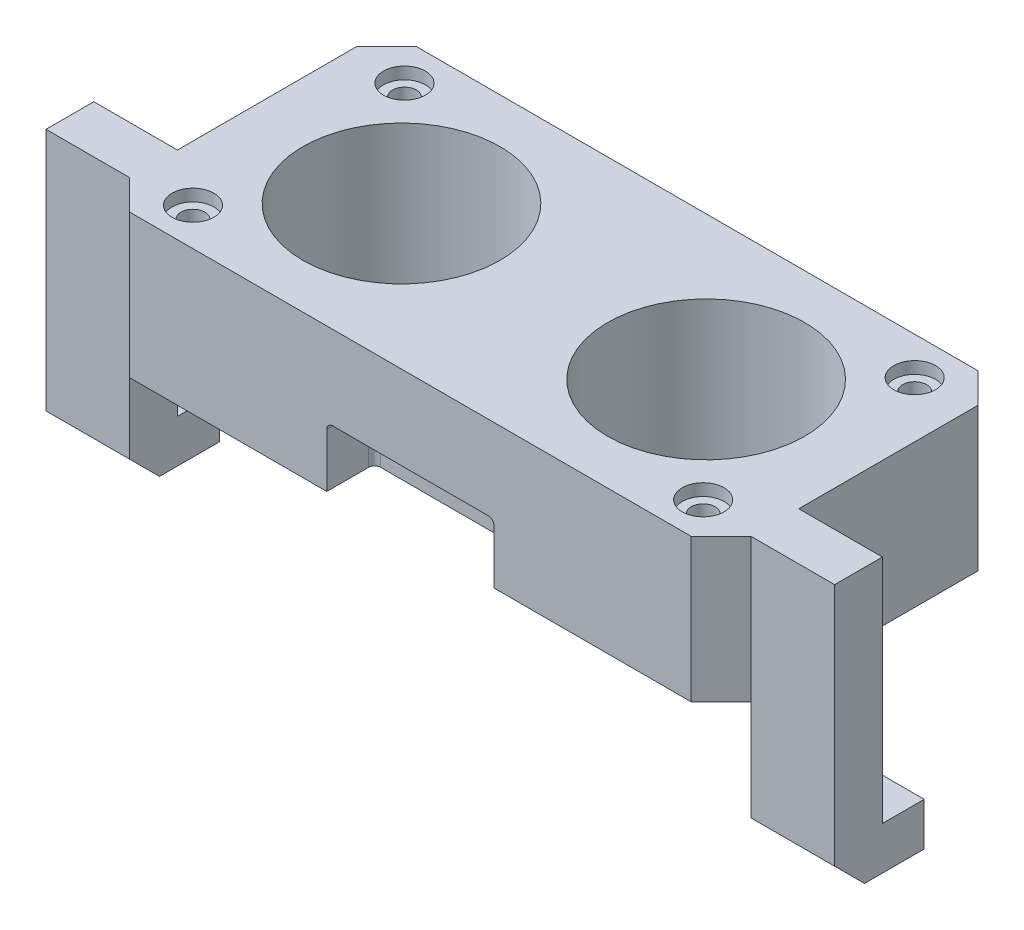
SolidWorks part; units mm, degrees
ref_plane "Front Plane" through (0, 0, 0) normal (0, 0, 1) x (1, 0, 0)
ref_plane "Top Plane" through (0, 0, 0) normal (0, 1, 0) x (1, 0, 0)
ref_plane "Right Plane" through (0, 0, 0) normal (1, 0, 0) x (0, 0, -1)
sketch "Sketch1" plane through (0, 0, 0) normal (0, 1, 0) x (1, 0, 0)
  line L0 (-12.75, 0) -> (12.75, 0) construction
  line L1 (-26, 12) -> (26, 12)
  line L2 (-26, 12) -> (-26, -12)
  line L3 (-26, -12) -> (26, -12)
  line L4 (26, 12) -> (26, -12)
  line L5 (-26, 12) -> (26, -12) construction
  line L6 (-26, -12) -> (26, 12) construction
  circle A0 centre (12.75, 0) radius 8.25
  circle A1 centre (-12.75, 0) radius 8.25
  point P0 (0, 0)
  point P9 (0, 0)
  dimension "D3" = 16.5
  dimension "D1" = 52
  dimension "D2" = 24
  dimension "D4" = 25.5
extrude "Boss-Extrude1" add sketch "Sketch1" along normal blind 12
sketch "Sketch2" plane through (0, 12, 0) normal (0, 1, 0) x (1, 0, 0)
  line L1 (-21.35, 8.85) -> (21.35, 8.85) construction
  line L2 (-21.35, 8.85) -> (-21.35, -8.85) construction
  line L3 (-21.35, -8.85) -> (21.35, -8.85) construction
  line L4 (21.35, 8.85) -> (21.35, -8.85) construction
  line L5 (-21.35, 8.85) -> (21.35, -8.85) construction
  line L6 (-21.35, -8.85) -> (21.35, 8.85) construction
  circle A0 centre (-21.35, 8.85) radius 1
  circle A1 centre (21.35, 8.85) radius 1
  circle A2 centre (21.35, -8.85) radius 1
  circle A3 centre (-21.35, -8.85) radius 1
  point P0 (0, 0)
  dimension "D3" = 2
  dimension "D1" = 17.7
  dimension "D2" = 42.7
extrude "Cut-Extrude1" cut sketch "Sketch2" against normal through all
sketch "Sketch3" plane through (0, 12, 0) normal (0, 1, 0) x (1, 0, 0)
  circle A20 centre (-21.35, 8.85) radius 1.75
  circle A21 centre (21.35, 8.85) radius 1.75
  circle A23 centre (21.35, -8.85) radius 1.75
  circle A24 centre (-21.35, -8.85) radius 1.75
  dimension "D1" = 3.5
extrude "Cut-Extrude2" cut sketch "Sketch3" against normal blind 1
sketch "Sketch4" plane through (0, 0, 0) normal (0, -1, 0) x (1, 0, 0)
  line L0 (26, -12) -> (-26, -12) construction
  line L1 (-6, -12) -> (6, -12)
  line L2 (-6, -12) -> (-6, -5)
  line L3 (-6, -5) -> (6, -5)
  line L4 (6, -12) -> (6, -5)
  line L5 (0, -5) -> (0, 0)
  line M14 (-26, -12) -> (26, -12)
  dimension "D1" = 7
  dimension "D2" = 12
extrude "Cut-Extrude3" cut sketch "Sketch4" against normal blind 5 contours L4 L3 L2 M14 region at (0, 0, -8.5)
fillet "Fillet3" radius 0.5 5 edges at (-6, 5, -8.5) (6, 5, -8.5) (6, 2.5, -5) (0, 5, -5) (-6, 2.5, -5)
chamfer "Chamfer1" distance 2.5 4 edges at (26, 6, 12) (26, 6, -12) (-26, 6, -12) (-26, 6, 12)
sketch "Sketch5" plane through (0, 0, 0) normal (0, -1, 0) x (1, 0, 0)
  line L0 (-23.5, 12) -> (23.5, 12) construction
  line L1 (-7, 16) -> (7, 16)
  line L2 (-7, 16) -> (-7, 8)
  line L3 (-7, 8) -> (7, 8)
  line L4 (7, 16) -> (7, 8)
  line L5 (-7, 16) -> (7, 8) construction
  line L6 (-7, 8) -> (7, 16) construction
  point P0 (0, 12)
  dimension "D1" = 8
  dimension "D2" = 14
extrude "Cut-Extrude4" cut sketch "Sketch5" against normal up to surface (5 mm away) up to face at (0, 5, -8.75)
fillet "Fillet4" radius 0.5 5 edges at (7, 2.5, 8) (7, 5, 10) (-7, 5, 10) (-7, 2.5, 8) (0, 5, 8)
sketch "Sketch6" plane through (26, 0, 0) normal (1, 0, 0) x (0, 0, -1)
  line L0 (-5.5, 0) -> (-5.5, 12)
  line L1 (-9.5, 0) -> (9.5, 0) construction
  line L2 (-5.5, 12) -> (-9.5, 12)
  line L3 (-9.5, 12) -> (-9.5, 0) construction
  line L4 (-9.5, 12) -> (-9.5, -10.9095)
  line L5 (-9.5, -10.9095) -> (-2, -10.9095)
  line L6 (-2, -10.9095) -> (-2, -7.3095)
  line L7 (-2, -7.3095) -> (-5.5, -7.3095)
  line L8 (-5.5, -7.3095) -> (-5.5, 0)
  line L10 (-9.5, 12) -> (9.5, 12) construction
  dimension "D1" = 3.6
  dimension "D2" = 4
extrude "Boss-Extrude2" add sketch "Sketch6" along normal blind 7
extrude "Boss-Extrude3" add sketch "Sketch6<2>" against normal blind 7 from surface starting at face at (-26, 6, 0)
sketch "Sketch6<2>" plane through (26, 0, 0) normal (1, 0, 0) x (0, 0, -1) same geometry as "Sketch6"
chamfer "Chamfer2" distance 2.5 2 edges at (29.5, -10.9095, 9.5) (-29.5, -10.9095, 9.5)
